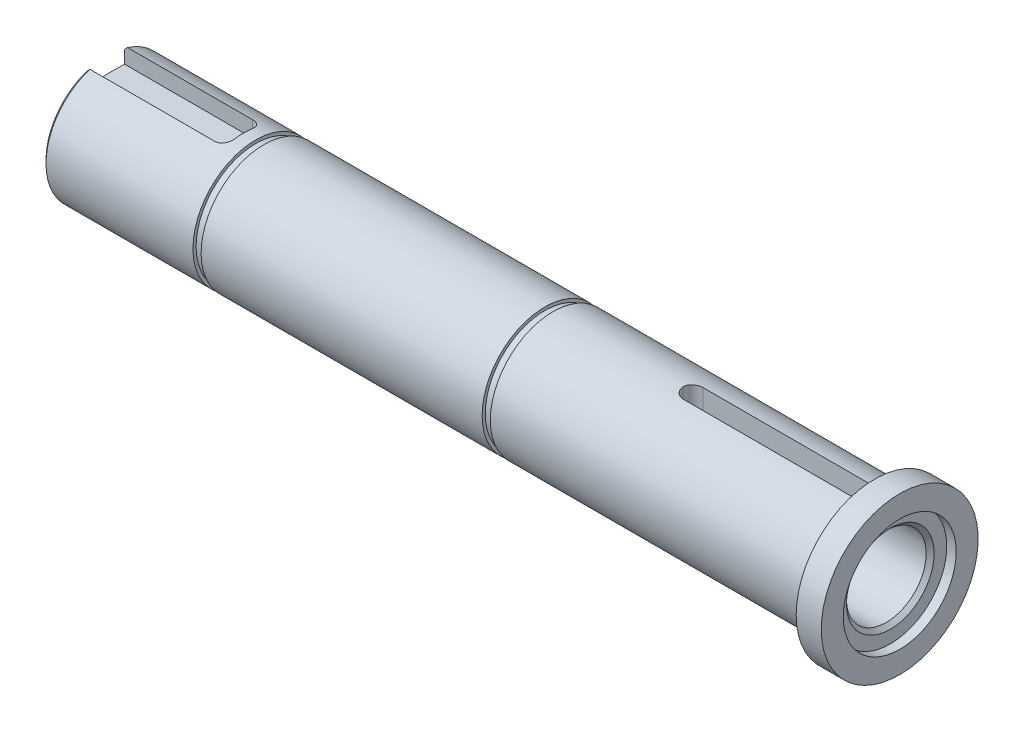
SolidWorks part; units mm, degrees
material "AISI 4130 Steel, normalized at 870C"
ref_plane "Front Plane" through (0, 0, 0) normal (0, 0, 1) x (1, 0, 0)
ref_plane "Top Plane" through (0, 0, 0) normal (0, 1, 0) x (1, 0, 0)
ref_plane "Right Plane" through (0, 0, 0) normal (1, 0, 0) x (0, 0, -1)
sketch "Sketch1" plane through (0, 0, 0) normal (0, 0, 1) x (1, 0, 0)
  line L0 (-9.141, 0) -> (9837.7259, 0) construction
  line L1 (0, 0) -> (0, 10)
  line L2 (0, 10) -> (23.92, 10)
  line L3 (122.56, 10) -> (122.56, 12.5)
  line L4 (122.56, 12.5) -> (126.56, 12.5)
  line L5 (126.56, 12.5) -> (126.56, 9)
  line L6 (126.56, 9) -> (125.06, 9)
  line L7 (125.06, 9) -> (125.06, 6.375)
  line L8 (125.06, 6.375) -> (87.56, 6.375) construction
  line L9 (87.56, 6.375) -> (87.56, 0) construction
  line L10 (87.56, 0) -> (0, 0)
  line L11 (125.06, 6.375) -> (125.06, 0)
  line L12 (125.06, 0) -> (87.56, 0)
  line L13 (23.92, 10) -> (23.92, 9.5)
  line L14 (23.92, 9.5) -> (25.22, 9.5)
  line L15 (25.22, 9.5) -> (25.22, 10)
  line L16 (25.22, 10) -> (70.01, 10)
  line L17 (71.31, 10) -> (71.31, 9.5)
  line L18 (71.31, 9.5) -> (70.01, 9.5)
  line L19 (70.01, 9.5) -> (70.01, 10)
  line L20 (71.31, 10) -> (122.56, 10)
  dimension "D1" = 20
  dimension "D2" = 25
  dimension "D3" = 6.375
  dimension "D4" = 4
  dimension "D5" = 126.56
  dimension "D6" = 35
  dimension "D7" = 1.5
  dimension "D8" = 18
  dimension "D9" = 2.6926
  dimension "D10" = 23.92
  dimension "D11" = 1.3
  dimension "D12" = 19
  dimension "D13" = 55.25
  dimension "D14" = 19
revolve "Revolve1" add sketch "Sketch1" angle 360 about L0
hole_wizard "1/2 (0.5) Diameter Hole1" positions "Sketch2" profile "Sketch4" hole size "1/2" standard "ANSI Inch"
sketch "Sketch2" plane through (125.06, 0, 0) normal (1, 0, 0) x (0, 0, -1)
  point P0 (0, 0)
sketch "Sketch4" plane through (125.06, 0, 0) normal (0, 1, 0) x (0, 0, -1)
  line L0 (0, 0) -> (0, 41.8155)
  line L1 (0, 41.8155) -> (6.35, 38)
  line L2 (6.35, 38) -> (6.35, 0.635)
  line L3 (6.35, 0.635) -> (6.985, 0)
  line L5 (6.985, 0) -> (0, 0)
  line L6 (-6.35, 0.635) -> (-6.985, 0) construction
  line L10 (0, 41.8155) -> (-6.35, 38) construction
  line L11 (0, -6.35) -> (0, 107.95) construction
  dimension "Hole Dia." = 12.7
  dimension "Hole Depth" = 38
  dimension "Near C'Sink Dia." = 13.97
  dimension "Near C'Sink Angle" = 90
  dimension "Drill Angle" = 118
sketch "Sketch5" plane through (125.06, 0, 0) normal (1, 0, 0) x (0, 0, -1)
  line L3 (0, 6.35) -> (0, 0) construction
  circle A0 centre (0, 0) radius 6.35 construction
  circle A1 centre (0, 0) radius 9
  circle A2 centre (0, 0) radius 9
  circle A3 centre (0, 0) radius 6.35
  dimension "D1" = 0
fillet "Fillet1" radius 0.5 1 edges at (122.56, 0, 10)
sketch "Sketch6" plane through (0, 0, 0) normal (-1, 0, 0) x (0, 0, 1)
  line L0 (-3, 9.5394) -> (-3, 7)
  line L1 (-3, 7) -> (3, 7)
  line L2 (3, 7) -> (3, 9.5394)
  line L3 (0, 7) -> (0, 0) construction
  circle A1 centre (0, 0) radius 10
  circle A2 centre (0, 0) radius 10
  circle M6 centre (0, 0) radius 10
  dimension "D2" = 6
  dimension "D3" = 3
  dimension "D1" = 0
extrude "Cut-Extrude2" cut sketch "Sketch6" against normal blind 22 contours L1 L2 L0 M6
fillet "Fillet2" radius 1.5875 2 edges at (22, 8.2697, 3) (22, 8.2697, -3)
chamfer "Chamfer2" distance 0.5 angle 45 1 edges at (0, -10, 0)
hole_wizard "M8x1.25 Tapped Hole1" positions "Sketch7" profile "Sketch8" tap size "M8x1.25" standard "ANSI Metric"
sketch "Sketch7" plane through (0, 0, 0) normal (-1, 0, 0) x (0, 0, 1)
  point P0 (0, 0)
sketch "Sketch8" plane through (0, 0, 0) normal (0, 1, 0) x (0, 0, 1)
  line L0 (0, 0) -> (0, 32.0429)
  line L1 (0, 32.0429) -> (3.4, 30)
  line L2 (3.4, 30) -> (3.4, 0)
  line L5 (3.4, 0) -> (0, 0)
  line L10 (0, 32.0429) -> (-3.4, 30) construction
  line L11 (0, -6.35) -> (0, 107.95) construction
  dimension "Tap Drill Dia." = 6.8
  dimension "Tap Drill Depth" = 30
  dimension "Drill Angle" = 118
cosmetic thread "Hole Thread1" parameters "D1"=26, "D2"=8
ref_plane "Plane1" through (0, 10, 0) normal (0, 1, 0) x (1, 0, 0)
sketch "Sketch9" plane through (0, 10, 0) normal (0, 1, 0) x (1, 0, 0)
  line L1 (126.56, -12.5) -> (126.56, 12.5) construction
  line L2 (121.76, 1.5875) -> (121.76, -1.5875)
  line L3 (126.56, -12.5) -> (126.56, 12.5) construction
  line L4 (126.56, 0) -> (92.06, 0) construction
  line L5 (92.06, 1.5875) -> (92.06, -1.5875)
  line L6 (92.06, 1.5875) -> (121.76, 1.5875)
  line L8 (92.06, -1.5875) -> (121.76, -1.5875)
  line L11 (122.56, 12.5) -> (122.56, -12.5) construction
  dimension "D1" = 3.175
  dimension "D2" = 34.5
  dimension "D6" = 0.8
extrude "Cut-Extrude3" cut sketch "Sketch9" against normal up to next
fillet "Fillet4" radius 1.5875 4 edges at (92.06, 8.0108, 1.5875) (121.76, 8.0108, 1.5875) (121.76, 8.0108, -1.5875) (92.06, 8.0108, -1.5875)
